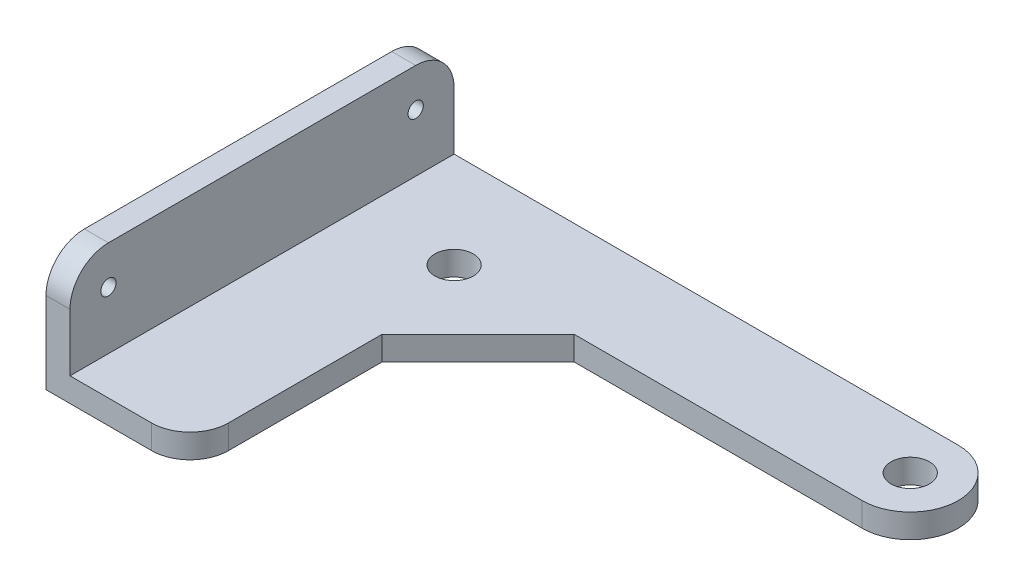
SolidWorks part; units mm, degrees
ref_plane "Front Plane" through (0, 0, 0) normal (0, 0, 1) x (1, 0, 0)
ref_plane "Top Plane" through (0, 0, 0) normal (0, 1, 0) x (1, 0, 0)
ref_plane "Right Plane" through (0, 0, 0) normal (1, 0, 0) x (0, 0, -1)
sketch "Sketch1" plane through (0, 0, 0) normal (0, 1, 0) x (1, 0, 0)
  line L0 (0, 0) -> (0, 400)
  line L1 (0, 400) -> (550, 400)
  line L2 (250, 300) -> (550, 300)
  line L3 (550, 300) -> (550, 400) construction
  line L4 (0, 0) -> (150, 0)
  line L5 (150, 0) -> (150, 200)
  line L6 (150, 200) -> (250, 300)
  line L7 (25, 0) -> (25, 400)
  arc A0 (550, 400) -> (550, 300) centre (550, 350) cw
  dimension "D3" = 50
  dimension "D1" = 400
  dimension "D2" = 400
  dimension "D4" = 45
  dimension "D5" = 150
  dimension "D6" = 100
  dimension "D7" = 25
extrude "Boss-Extrude2" add sketch "Sketch1" along normal blind 25 contours L2 L3 L1 L7 L4 L5 L6 | L3 A0 region at (203.0702, 0, -266.6667) region at (571.2207, 0, -350)
extrude "Boss-Extrude3" add sketch "Sketch1<4>" along normal blind 125 contours L4 L7 L1 L0 region at (12.5, 0, -200)
sketch "Sketch1<4>" plane through (0, 0, 0) normal (0, 1, 0) x (1, 0, 0) same geometry as "Sketch1"
fillet "Fillet1" radius 40 1 edges at (150, 12.5, 0)
sketch "Sketch2" plane through (0, 25, 0) normal (0, 1, 0) x (1, 0, 0)
  line L1 (150, 40) -> (150, 200) construction
  circle A0 centre (550, 350) radius 20
  arc A1 (550, 300) -> (550, 400) centre (550, 350) ccw construction
  circle A2 centre (125, 300) radius 20
  dimension "D1" = 40
  dimension "D3" = 40
  dimension "D2" = 25
extrude "Cut-Extrude1" cut sketch "Sketch2" against normal through all contours A2 | A0
fillet "Fillet2" radius 40 2 edges at (12.5, 125, 0) (12.5, 125, -400)
sketch "Sketch3" plane through (25, 0, 0) normal (1, 0, 0) x (0, 0, -1)
  line L0 (200, 125) -> (200, 153.6851) construction
  line L1 (40, 125) -> (360, 125) construction
  circle A11 centre (40, 85) radius 7.94
  circle A12 centre (360, 85) radius 7.94
  dimension "D1" = 15.88
extrude "Cut-Extrude2" cut sketch "Sketch3" against normal through all
